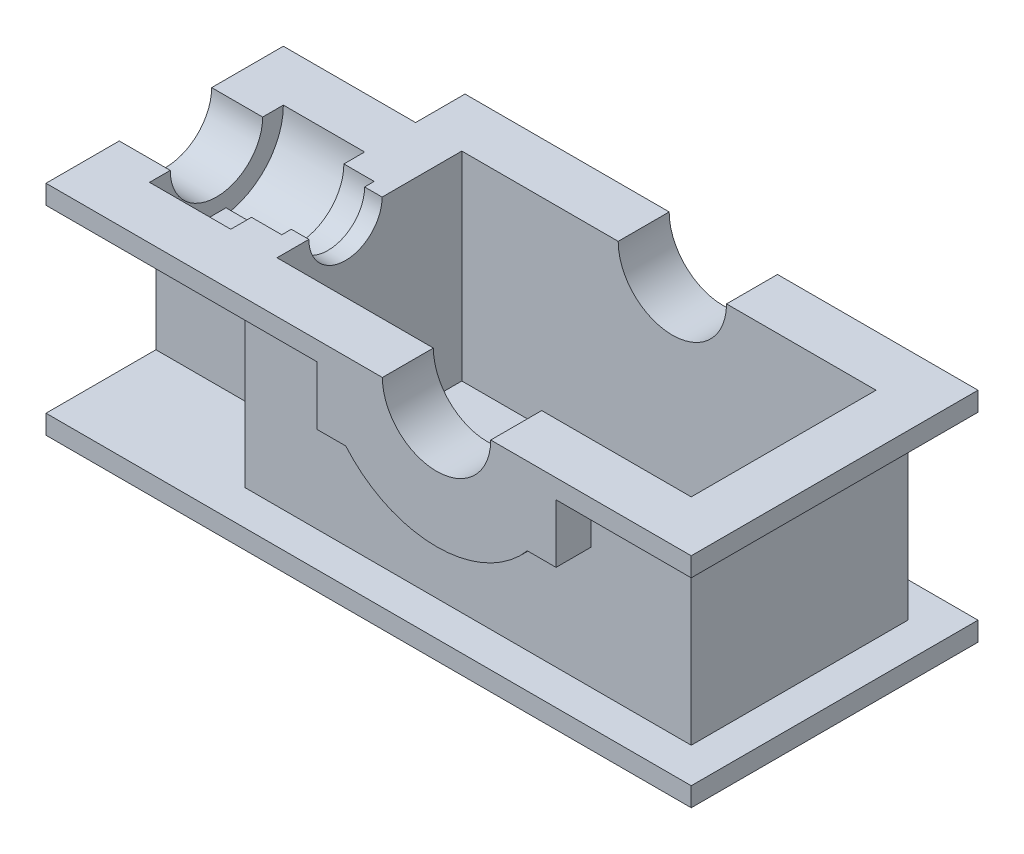
SolidWorks part; units mm, degrees
ref_plane "Спереди" through (0, 0, 0) normal (0, 0, 1) x (1, 0, 0)
ref_plane "Сверху" through (0, 0, 0) normal (0, 1, 0) x (1, 0, 0)
ref_plane "Справа" through (0, 0, 0) normal (1, 0, 0) x (0, 0, -1)
sketch "Эскиз1" plane through (0, 0, 0) normal (0, 1, 0) x (1, 0, 0)
  line L1 (0, 0) -> (313.8616, 0)
  line L2 (-8.1384, 148.982) -> (-8.1384, 180)
  line L3 (-8.1384, 180) -> (313.8616, 180)
  line L4 (313.8616, 0) -> (313.8616, 180)
  line L5 (0, 0) -> (-91.1384, 0)
  line L7 (-8.1384, 148.982) -> (-91.1384, 148.982)
  line L8 (-91.1384, 0) -> (-91.1384, 148.982)
  dimension "D1" = 180
  dimension "D2" = 148.982
  dimension "D3" = 322
  dimension "D4" = 83
extrude "Бобышка-Вытянуть1" add sketch "Эскиз1" along normal blind 12
sketch "Эскиз2" plane through (0, 12, 0) normal (0, 1, 0) x (1, 0, 0)
  line L0 (-91.1384, 0) -> (313.8616, 0) construction
  line L1 (79.0126, 0) -> (229.0126, 0)
  line L2 (79.0126, 0) -> (79.0126, 32)
  line L3 (79.0126, 32) -> (229.0126, 32)
  line L4 (229.0126, 0) -> (229.0126, 32)
  line L5 (313.8616, 180) -> (-8.1384, 180) construction
  line L6 (79.0126, 180) -> (229.0126, 180)
  line L7 (79.0126, 180) -> (79.0126, 148)
  line L8 (79.0126, 148) -> (229.0126, 148)
  line L9 (229.0126, 180) -> (229.0126, 148)
  line L10 (313.8616, 0) -> (313.8616, 180) construction
  line L11 (-8.1384, 148.982) -> (-91.1384, 148.982) construction
  line L12 (-8.1384, 123.982) -> (21.8616, 123.982)
  line L13 (-8.1384, 123.982) -> (-8.1384, 25.982)
  line L14 (-8.1384, 25.982) -> (21.8616, 25.982)
  line L15 (21.8616, 123.982) -> (21.8616, 25.982)
  line L16 (-91.1384, 148.982) -> (-91.1384, 0) construction
  line L17 (-91.1384, 123.982) -> (-59.1384, 123.982)
  line L18 (-91.1384, 123.982) -> (-91.1384, 25.982)
  line L19 (-91.1384, 25.982) -> (-59.1384, 25.982)
  line L20 (-59.1384, 123.982) -> (-59.1384, 25.982)
  dimension "D1" = 32
  dimension "D2" = 150
  dimension "D3" = 32
  dimension "D4" = 150
  dimension "D5" = 84.849
  dimension "D6" = 84.849
  dimension "D7" = 98
  dimension "D8" = 25
  dimension "D9" = 30
  dimension "D10" = 83
  dimension "D11" = 32
  dimension "D12" = 98
  dimension "D13" = 51
  dimension "D14" = 25
extrude "Бобышка-Вытянуть2" add sketch "Эскиз2" along normal blind 250
sketch "Эскиз3" plane through (0, 0, 0) normal (0, 0, 1) x (1, 0, 0)
  line L0 (79.0126, 262) -> (229.0126, 262) construction
  line L1 (229.0126, 262) -> (229.0126, 12) construction
  circle A0 centre (154.0126, 137) radius 34
  dimension "D1" = 68
  dimension "D2" = 125
  dimension "D3" = 75
extrude "Вырез-Вытянуть1" cut sketch "Эскиз3" against normal blind 180
sketch "Эскиз5" plane through (-91.1384, 0, 0) normal (-1, 0, 0) x (0, 0, 1)
  line L0 (-123.982, 262) -> (-25.982, 262) construction
  line L1 (-25.982, 262) -> (-25.982, 12) construction
  line L2 (-123.982, 262) -> (-123.982, 12) construction
  circle A0 centre (-74.982, 137) radius 29
  dimension "D1" = 58
  dimension "D2" = 125
  dimension "D3" = 49
  dimension "D4" = 49
extrude "Вырез-Вытянуть2" cut sketch "Эскиз5" against normal blind 102
sketch "Эскиз7" plane through (21.8616, 0, 0) normal (1, 0, 0) x (0, 0, -1)
  line L0 (25.982, 262) -> (123.982, 262) construction
  line L1 (123.982, 262) -> (123.982, 12) construction
  line L2 (25.982, 262) -> (25.982, 12) construction
  circle A0 centre (74.982, 137) radius 23
  dimension "D1" = 46
  dimension "D2" = 125
  dimension "D3" = 49
  dimension "D4" = 49
extrude "Вырез-Вытянуть3" cut sketch "Эскиз7" against normal blind 30
sketch "Эскиз8" plane through (0, 262, 0) normal (0, 1, 0) x (1, 0, 0)
  line L1 (-100.3584, 191.7087) -> (395.7307, 191.7087)
  line L2 (-100.3584, 191.7087) -> (-100.3584, -33.7109)
  line L3 (-100.3584, -33.7109) -> (395.7307, -33.7109)
  line L4 (395.7307, 191.7087) -> (395.7307, -33.7109)
extrude "Вырез-Вытянуть4" cut sketch "Эскиз8" against normal blind 125
sketch "Эскиз9" plane through (0, 137, 0) normal (0, 1, 0) x (1, 0, 0)
  line L0 (21.8616, 25.982) -> (21.8616, 123.982) construction
  line L1 (120.0126, 32) -> (21.8616, 32)
  line L2 (120.0126, 32) -> (120.0126, 0)
  line L3 (120.0126, 0) -> (-91.1384, 0)
  line L4 (-91.1384, 32) -> (-91.1384, 0)
  line L5 (188.0126, 32) -> (313.8616, 32)
  line L6 (188.0126, 32) -> (188.0126, 0)
  line L7 (188.0126, 0) -> (313.8616, 0)
  line L8 (313.8616, 32) -> (313.8616, 0)
  line L9 (188.0126, 148) -> (313.8616, 148)
  line L10 (188.0126, 148) -> (188.0126, 180)
  line L11 (188.0126, 180) -> (313.8616, 180)
  line L12 (313.8616, 148) -> (313.8616, 180)
  line L13 (313.8616, 148) -> (281.8616, 148)
  line L14 (313.8616, 148) -> (313.8616, 32)
  line L15 (313.8616, 32) -> (281.8616, 32)
  line L16 (281.8616, 148) -> (281.8616, 32)
  line L21 (-91.1384, 148.982) -> (-8.1384, 148.982)
  line L22 (-91.1384, 148.982) -> (-91.1384, 116.982)
  line L23 (-91.1384, 116.982) -> (21.8616, 116.982)
  line L24 (21.8616, 148) -> (21.8616, 116.982)
  line L26 (120.0126, 148) -> (21.8616, 148)
  line L27 (120.0126, 148) -> (120.0126, 180)
  line L28 (120.0126, 180) -> (-8.1384, 180)
  line L29 (-8.1384, 148.982) -> (-8.1384, 180)
  line L31 (-91.1384, 32) -> (-91.1384, 32.982)
  line L32 (-91.1384, 32.982) -> (21.8616, 32.982)
  line L33 (21.8616, 32) -> (21.8616, 32.982)
  line M22 (120.0126, 180) -> (79.0126, 180)
  line M23 (79.0126, 180) -> (79.0126, 148)
  line M24 (79.0126, 148) -> (120.0126, 148)
  line M25 (120.0126, 148) -> (120.0126, 180)
  dimension "D1" = 32
  dimension "D2" = 211.151
  dimension "D3" = 32
  dimension "D4" = 125.849
  dimension "D5" = 32
  dimension "D6" = 116
  dimension "D7" = 32
  dimension "D8" = 125.849
  dimension "D9" = 32
  dimension "D10" = 128.151
  dimension "D11" = 32
  dimension "D12" = 84
extrude "Бобышка-Вытянуть4" add sketch "Эскиз9" against normal blind 12 contours L29 L21 L22 L23 L24 L26 L28 M23 | M25 M22 M23 M24 | L9 L12 L11 L10 | L9 L16 L5 L14 | L8 L5 L6 L7 | L1 L33 L32 L31 L4 L3 L2 region at (13.6442, 137, -16.2665) region at (250.9371, 137, -16) region at (297.8616, 137, -90) region at (250.9371, 137, -164) region at (-4.1764, 137, -146.4788) region at (99.5126, 137, -164)
sketch "Эскиз10" plane through (0, 137, 0) normal (0, 1, 0) x (1, 0, 0)
  line L1 (120.0126, 148) -> (11.8616, 148)
  line L2 (120.0126, 148) -> (120.0126, 158)
  line L3 (120.0126, 158) -> (11.8616, 158)
  line L4 (11.8616, 148) -> (11.8616, 158)
  line L5 (21.8616, 97.982) -> (11.8616, 97.982)
  line L6 (21.8616, 97.982) -> (21.8616, 148)
  line L7 (21.8616, 148) -> (11.8616, 148)
  line L8 (11.8616, 97.982) -> (11.8616, 148)
  line L9 (21.8616, 51.982) -> (11.8616, 51.982)
  line L10 (21.8616, 51.982) -> (21.8616, 22)
  line L11 (21.8616, 22) -> (11.8616, 22)
  line L12 (11.8616, 51.982) -> (11.8616, 22)
  line L13 (120.0126, 32) -> (21.8616, 32)
  line L14 (120.0126, 32) -> (120.0126, 22)
  line L15 (120.0126, 22) -> (21.8616, 22)
  line L16 (21.8616, 32) -> (21.8616, 22)
  line L17 (188.0126, 32) -> (291.8616, 32)
  line L18 (188.0126, 32) -> (188.0126, 22)
  line L19 (188.0126, 22) -> (291.8616, 22)
  line L20 (291.8616, 32) -> (291.8616, 22)
  line L21 (188.0126, 148) -> (291.8616, 148)
  line L22 (188.0126, 148) -> (188.0126, 158)
  line L23 (188.0126, 158) -> (291.8616, 158)
  line L24 (291.8616, 148) -> (291.8616, 158)
  line L25 (291.8616, 148) -> (281.8616, 148)
  line L26 (291.8616, 148) -> (291.8616, 32)
  line L27 (291.8616, 32) -> (281.8616, 32)
  line L28 (281.8616, 148) -> (281.8616, 32)
  line M11 (10.8616, 97.982) -> (21.8616, 97.982)
  line M12 (21.8616, 97.982) -> (21.8616, 148)
  dimension "D1" = 10
  dimension "D2" = 10
  dimension "D3" = 10
  dimension "D4" = 10
  dimension "D5" = 10
  dimension "D6" = 10
  dimension "D7" = 10
extrude "Бобышка-Вытянуть5" add sketch "Эскиз10" against normal blind 125 contours L8 L1 M11 M12 | L21 L24 L23 L22 | L21 L28 L17 L26 | L9 L12 L11 L10 | L4 L3 L2 L1 | L20 L19 L18 L17 | L15 L14 L13 L16 region at (16.8616, 137, -122.991) region at (16.8616, 137, -36.991) region at (286.8616, 137, -90) region at (239.9371, 137, -153)
sketch "Эскиз12" plane through (-91.1384, 0, 0) normal (-1, 0, 0) x (0, 0, 1)
  line L0 (-148.982, 0) -> (0, 0) construction
  line L2 (-148.982, 125) -> (-148.982, 137) construction
  line L3 (-121.982, 137) -> (-116.982, 137)
  line L4 (-27.982, 137) -> (-32.982, 137)
  arc A0 (-116.982, 137) -> (-32.982, 137) centre (-74.982, 137) ccw
  arc A2 (-121.982, 137) -> (-27.982, 137) centre (-74.982, 137) ccw
  dimension "D3" = 84
  dimension "D4" = 94
  dimension "D1" = 137
  dimension "D2" = 74
extrude "Бобышка-Вытянуть6" add sketch "Эскиз12" against normal blind 83
sketch "Эскиз14" plane through (-91.1384, 0, 0) normal (-1, 0, 0) x (0, 0, 1)
  line L0 (-120.4243, 125) -> (-123.982, 125)
  line L1 (-25.982, 125) -> (-29.5397, 125)
  line L2 (-25.982, 125) -> (-25.982, 12)
  line L3 (-25.982, 12) -> (-123.982, 12)
  line L4 (-123.982, 125) -> (-123.982, 12)
  arc A0 (-120.4243, 125) -> (-29.5397, 125) centre (-74.982, 137) ccw
  dimension "D1" = 94
extrude "Вырез-Вытянуть5" cut sketch "Эскиз14" against normal blind 103
sketch "Эскиз16" plane through (-91.1384, 0, 0) normal (-1, 0, 0) x (0, 0, 1)
  line L0 (-158, 12) -> (-22, 12) construction
  line L1 (-80.982, 12) -> (-68.982, 12)
  line L2 (-80.982, 12) -> (-80.982, 99.152)
  line L3 (-80.982, 99.152) -> (-68.982, 99.152)
  line L4 (-68.982, 12) -> (-68.982, 99.152)
  line L5 (-148.982, 125) -> (-148.982, 137) construction
  point P6 (-71.0536, 88.671)
  point P9 (-74.982, 99.152)
  dimension "D1" = 74
  dimension "D2" = 12
extrude "Бобышка-Вытянуть7" add sketch "Эскиз16" against normal blind 103
sketch "Эскиз17" plane through (0, 0, 0) normal (0, 0, 1) x (1, 0, 0)
  line L1 (79.0126, 12) -> (229.0126, 12)
  line L2 (79.0126, 12) -> (79.0126, 88.2558)
  line L4 (229.0126, 12) -> (229.0126, 88.2558)
  line L11 (79.0126, 88.2558) -> (97.0126, 88.2558)
  line L15 (229.0126, 88.2558) -> (211.0126, 88.2558)
  arc A1 (97.0126, 88.2558) -> (211.0126, 88.2558) centre (154.0126, 137) ccw
extrude "Вырез-Вытянуть6" cut sketch "Эскиз17" against normal blind 22
sketch "Эскиз18" plane through (0, 0, -180) normal (0, 0, -1) x (-1, 0, 0)
  line L2 (-229.0126, 12) -> (-79.0126, 12)
  line L3 (-229.0126, 12) -> (-229.0126, 88.2558)
  line L5 (-79.0126, 12) -> (-79.0126, 88.2558)
  line L8 (-229.0126, 88.2558) -> (-211.0126, 88.2558)
  line L12 (-79.0126, 88.2558) -> (-97.0126, 88.2558)
  arc A1 (-211.0126, 88.2558) -> (-97.0126, 88.2558) centre (-154.0126, 137) ccw
extrude "Вырез-Вытянуть7" cut sketch "Эскиз18" against normal blind 22
